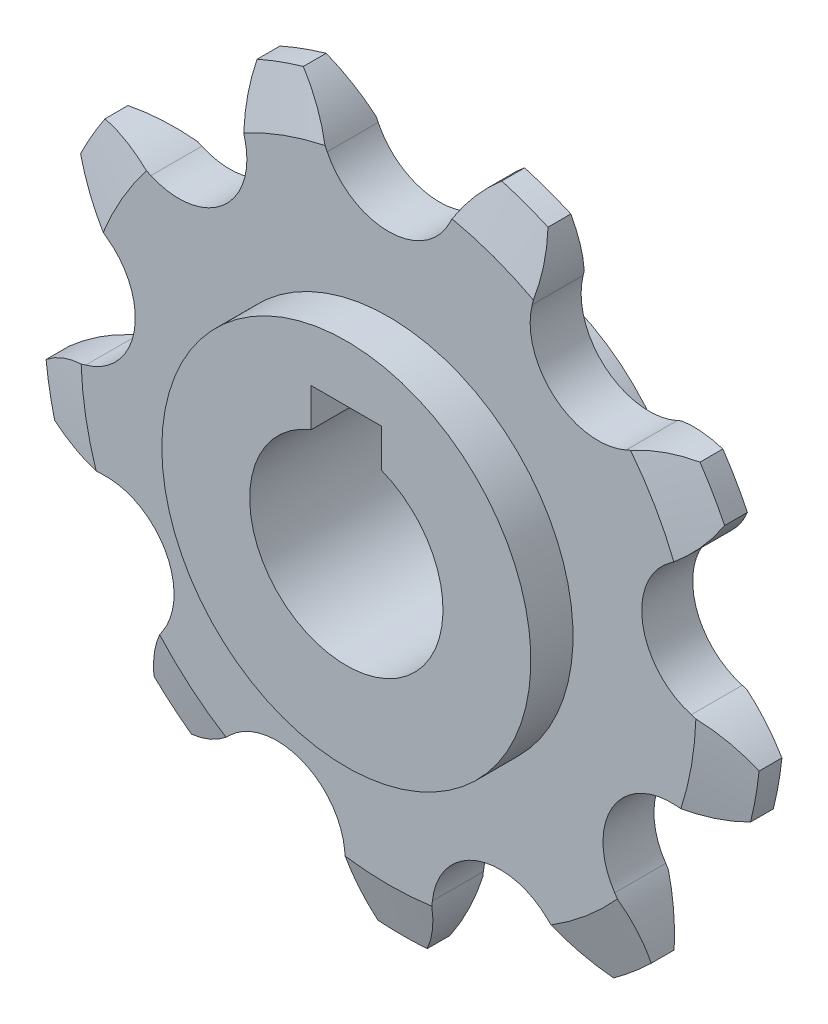
SolidWorks part; units mm, degrees
material "Acier allié"
ref_plane "Plan de face" through (0, 0, 0) normal (0, 0, 1) x (1, 0, 0)
ref_plane "Plan de dessus" through (0, 0, 0) normal (0, 1, 0) x (1, 0, 0)
ref_plane "Plan de droite" through (0, 0, 0) normal (1, 0, 0) x (0, 0, -1)
ref_axis "Axe pignon" through (0, 0, 0) along (0, 0, 1)
sketch "Esquisse1" plane through (0, 0, 0) normal (1, 0, 0) x (0, 0, -1)
  line L0 (0, 0) -> (-12.8849, 0) construction
  line L1 (-5.8, 20.4) -> (-6.6, 17.5)
  line L2 (0, 5.5) -> (-9, 5.5)
  line L3 (0, 5.5) -> (0, 10.5)
  line L4 (-4.5, 20.4) -> (-5.8, 20.4)
  line L5 (-9, 5.5) -> (-9, 10.5)
  line L6 (-6.6, 10.5) -> (-9, 10.5)
  line L7 (-4.5, 20.4) -> (-3.7, 17.5)
  line L8 (-3.7, 10.5) -> (0, 10.5)
  line L9 (-6.6, 10.5) -> (-6.6, 17.5)
  line L10 (-3.7, 10.5) -> (-3.7, 17.5)
  line L11 (-5.15, 20.4) -> (-5.15, 15.1777) construction
  dimension "D1" = 9
  dimension "D2" = 11
  dimension "D3" = 40.8
  dimension "D4" = 3.7
  dimension "D5" = 2.4
  dimension "D6" = 21
  dimension "D7" = 35
  dimension "D8" = 1.3
  dimension "D9" = 2.9
revolve "Révolution1" add sketch "Esquisse1" angle 360 about L0
ref_plane "Plan milieu denture" through (0, 0, 5.15) normal (0, 0, 1) x (1, 0, 0)
sketch "Esquisse2" plane through (0, 0, 0) normal (0, 0, 1) x (1, 0, 0)
  line L1 (-2, 7.3) -> (2, 7.3)
  line L2 (-2, 7.3) -> (-2, 0)
  line L3 (-2, 0) -> (2, 0)
  line L4 (2, 7.3) -> (2, 0)
  circle A0 centre (0, 0) radius 5.5 construction
  dimension "D1" = 4
  dimension "D2" = 12.8
extrude "Enlèv. mat.-Extru.1" cut sketch "Esquisse2" along normal through all
sketch "Esquisse3" plane through (0, 0, 5.15) normal (0, 0, 1) x (1, 0, 0)
  line L0 (0, 18.5662) -> (-11.9341, 14.2225)
  line L1 (-16.0788, -9.2831) -> (-6.35, -17.4465)
  line L2 (-6.35, -17.4465) -> (6.35, -17.4465)
  line L3 (6.35, -17.4465) -> (16.0788, -9.2831)
  line L4 (16.0788, -9.2831) -> (18.2841, 3.224)
  line L5 (18.2841, 3.224) -> (11.9341, 14.2225)
  line L6 (11.9341, 14.2225) -> (0, 18.5662)
  line L7 (-11.9341, 14.2225) -> (-18.2841, 3.224)
  line L8 (-18.2841, 3.224) -> (-16.0788, -9.2831)
  circle A0 centre (0, 0) radius 18.5662 construction
  dimension "D1" = 12.7
sketch "Esquisse4" plane through (0, 0, 5.15) normal (0, 0, 1) x (1, 0, 0)
  line L0 (0, 0) -> (0, 18.5662) construction
  line L1 (0, 0) -> (-10.5503, 28.9867) construction
  arc A0 (-3.4882, 16.8784) -> (3.4882, 16.8784) centre (0, 18.5662) ccw
  circle A1 centre (-11.9341, 14.2225) radius 3.875 construction
  circle A2 centre (11.9341, 14.2225) radius 3.875 construction
  arc A3 (-3.4882, 16.8784) -> (-5.6452, 19.6034) centre (-10.6895, 13.3941) ccw
  arc A4 (3.4882, 16.8784) -> (5.6452, 19.6034) centre (10.6895, 13.3941) cw
  arc A5 (-5.6452, 19.6034) -> (5.6452, 19.6034) centre (0, 0) cw
  circle A6 centre (0, 0) radius 20.4 construction
  circle A7 centre (0, 0) radius 14.6912 construction
  dimension "D1" = 7.75
  dimension "D2" = 29.3823
  dimension "D5" = 8
  dimension "D3" = 20
  dimension "D4" = 2.8
extrude "Enlèv. mat.-Extru.2" cut sketch "Esquisse4" against normal through all and the other way through all
pattern_circular "Répétition circulaire1" count 9 over 360 about axis through (0, 0, 0) along (0, 0, 1) of "Enlèv. mat.-Extru.2"
